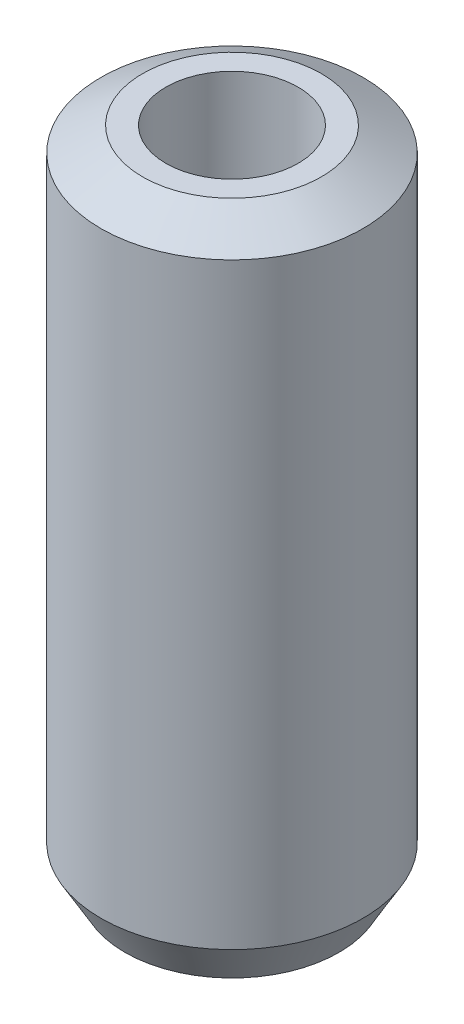
SolidWorks part; units mm, degrees
ref_plane "Front Plane" through (0, 0, 0) normal (0, 0, 1) x (1, 0, 0)
ref_plane "Top Plane" through (0, 0, 0) normal (0, 1, 0) x (1, 0, 0)
ref_plane "Right Plane" through (0, 0, 0) normal (1, 0, 0) x (0, 0, -1)
sketch "Sketch1" plane through (0, 0, 0) normal (0, 1, 0) x (1, 0, 0)
  circle A0 centre (0, 0) radius 30
  dimension "SHAFT_OD" = 60
extrude "Boss-Extrude1" add sketch "Sketch1" along normal blind 151.7705
sketch "Sketch2" plane through (0, 0, 0) normal (0, 1, 0) x (1, 0, 0)
  circle A0 centre (0, 0) radius 15.1396
  dimension "BORE_D" = 30.2791
extrude "Cut-Extrude1" cut sketch "Sketch2" along normal through all
chamfer "Chamfer1" distance 5.4962 angle 60 2 edges at (0, 151.7705, 30) (0, 0, 30) first distance on face at (0, 151.7705, 30) first distance on face at (0, 0, 15.1396)
